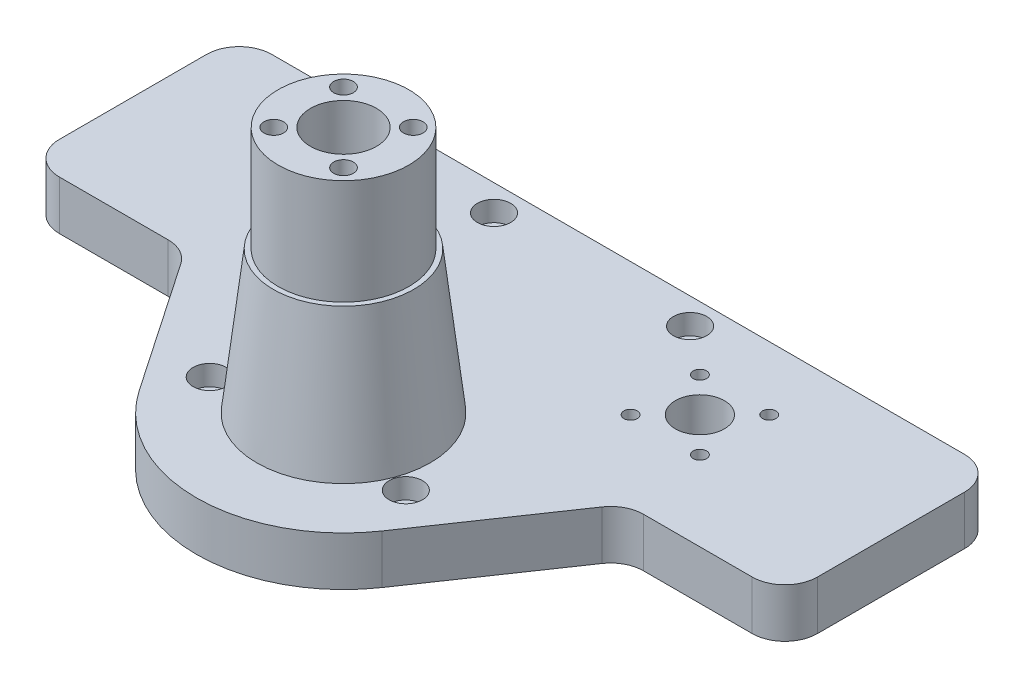
SolidWorks part; units mm, degrees
material "PLA Infill"
ref_plane "Front Plane" through (0, 0, 0) normal (0, 0, 1) x (1, 0, 0)
ref_plane "Top Plane" through (0, 0, 0) normal (0, 1, 0) x (1, 0, 0)
ref_plane "Right Plane" through (0, 0, 0) normal (1, 0, 0) x (0, 0, -1)
sketch "Sketch1" plane through (0, 0, 0) normal (0, 1, 0) x (1, 0, 0)
  line L0 (0, 0) -> (55, 54.0672) construction
  line L1 (55, 54.0672) -> (-55, 54.0672) construction
  line L2 (-55, 54.0672) -> (0, 0) construction
  line L3 (-79.7903, 37.1722) -> (-37.1854, -25.3425) construction
  line L4 (-55, 84.0672) -> (55, 84.0672)
  line L5 (37.1854, -25.3425) -> (79.7903, 37.1722) construction
  line L6 (-55, 84.0672) -> (-106, 84.0672)
  line L7 (-116, 74.0672) -> (-116, 29.0672)
  line L8 (-106, 19.0672) -> (-72.7378, 19.0672)
  line L9 (-64.4743, 14.6989) -> (-37.1854, -25.3425)
  line L10 (0, -1000) -> (0, 49000) construction
  line L11 (64.4743, 14.6989) -> (37.1854, -25.3425)
  line L12 (106, 19.0672) -> (72.7378, 19.0672)
  line L13 (116, 74.0672) -> (116, 29.0672)
  line L14 (55, 84.0672) -> (106, 84.0672)
  circle A0 centre (-55, 54.0672) radius 30 construction
  circle A1 centre (55, 54.0672) radius 30 construction
  circle A2 centre (0, 0) radius 45 construction
  arc A3 (-79.7903, 37.1722) -> (-55, 84.0672) centre (-55, 54.0672) cw construction
  arc A4 (55, 84.0672) -> (79.7903, 37.1722) centre (55, 54.0672) cw construction
  arc A5 (-37.1854, -25.3425) -> (37.1854, -25.3425) centre (0, 0) ccw
  arc A6 (-72.7378, 19.0672) -> (-64.4743, 14.6989) centre (-72.7378, 9.0672) cw
  arc A7 (-116, 29.0672) -> (-106, 19.0672) centre (-106, 29.0672) ccw
  arc A8 (-106, 84.0672) -> (-116, 74.0672) centre (-106, 74.0672) ccw
  arc A9 (72.7378, 19.0672) -> (64.4743, 14.6989) centre (72.7378, 9.0672) ccw
  arc A10 (116, 29.0672) -> (106, 19.0672) centre (106, 29.0672) cw
  arc A11 (106, 84.0672) -> (116, 74.0672) centre (106, 74.0672) cw
  point P23 (-67.4514, 19.0672)
  dimension "D3" = 60
  dimension "D4" = 90
  dimension "D5" = 10
  dimension "D6" = 61
  dimension "D1" = 110
  dimension "D2" = 77.125
  dimension "D7" = 35
extrude "Main Body" add sketch "Sketch1" along normal blind 15 contours A5 L11 A9 L12 A10 L13 A11 L14 L4 L6 A8 L7 A7 L8 A6 L9
sketch "Sketch3" plane through (0, 15, 0) normal (0, 1, 0) x (1, 0, 0)
  circle A0 centre (0, 0) radius 45 construction
  circle A1 centre (0, 0) radius 45 construction
  circle A2 centre (0, 0) radius 21.5
  dimension "D1" = 43
extrude "Front Extrusion" add sketch "Sketch3" along normal blind 75.7
ref_plane "First Bearing Section" through (0, 58.5, 0) normal (0, 1, 0) x (1, 0, 0)
sketch "Front Loft" plane through (0, 58.5, 0) normal (0, 1, 0) x (1, 0, 0)
  circle A0 centre (0, 0) radius 21.5
  dimension "D1" = 43
sketch "Back Loft" plane through (0, 15, 0) normal (0, 1, 0) x (1, 0, 0)
  circle A0 centre (0, 0) radius 26.5
  dimension "D1" = 53
loft "Lofted Taper" add profiles "Front Loft", "Back Loft" connector at (0, 58.5, 21.5) connector at (0, 15, 26.5)
sketch "Sketch4" plane through (0, 0, 0) normal (0, -1, 0) x (1, 0, 0)
  line L0 (0, -1000) -> (0, 49000) construction
  line L1 (-45, 0) -> (45, 0) construction
  line L2 (-85, -54.0672) -> (-25, -54.0672) construction
  line L3 (55, -54.0672) -> (-55, -54.0672) construction
  line L4 (-55, -24.0672) -> (-55, -84.0672) construction
  line L5 (-10.6773, 10.6773) -> (0, 0) construction
  line L6 (-10.6773, -10.6773) -> (0, 0) construction
  line L7 (-65.6066, -43.4606) -> (-55, -54.0672) construction
  line L8 (-106, -84.0672) -> (106, -84.0672) construction
  line L9 (106, -84.0672) -> (-106, -84.0672) construction
  line L10 (-30, -76.0672) -> (0, -76.0672) construction
  line L11 (-30, -76.0672) -> (-30, 10.9328) construction
  line L12 (-30, 10.9328) -> (0, 10.9328) construction
  line L13 (0, -76.0672) -> (0, 10.9328) construction
  circle A0 centre (55, -54.0672) radius 30 construction
  circle A1 centre (0, 0) radius 45 construction
  circle A2 centre (-55, -54.0672) radius 30 construction
  circle A3 centre (55, -54.0672) radius 30 construction
  circle A4 centre (0, 0) radius 45 construction
  circle A5 centre (-55, -54.0672) radius 30 construction
  circle A6 centre (0, 0) radius 10.1
  circle A7 centre (-55, -54.0672) radius 7.5
  circle A10 centre (-10.6773, 10.6773) radius 3
  circle A13 centre (-10.6773, -10.6773) radius 3
  circle A14 centre (-65.6066, -43.4606) radius 2.05
  circle A15 centre (-65.6066, -64.6738) radius 2.05
  circle A16 centre (-44.3934, -64.6738) radius 2.05
  circle A17 centre (-44.3934, -43.4606) radius 2.05
  circle A18 centre (55, -54.0672) radius 7.5
  circle A19 centre (65.6066, -64.6738) radius 2.05
  circle A20 centre (44.3934, -64.6738) radius 2.05
  circle A21 centre (44.3934, -43.4606) radius 2.05
  circle A22 centre (65.6066, -43.4606) radius 2.05
  circle A23 centre (10.6773, -10.6773) radius 3
  circle A24 centre (10.6773, 10.6773) radius 3
  circle A25 centre (-30, -76.0672) radius 3
  circle A26 centre (-30, 10.9328) radius 3
  circle A27 centre (30, -76.0672) radius 3
  circle A28 centre (30, 10.9328) radius 3
  dimension "D1" = 20.2
  dimension "D2" = 15
  dimension "D4" = 6
  dimension "D5" = 45
  dimension "D7" = 4.1
  dimension "D9" = 6
  dimension "D3" = 15.1
  dimension "D6" = 15
  dimension "D8" = 45
  dimension "D10" = 30
  dimension "D11" = 8
  dimension "D12" = 87
extrude "Bolt Holes" cut sketch "Sketch4" against normal through all
sketch "Sketch5" plane through (0, 0, 0) normal (0, -1, 0) x (1, 0, 0)
  line L0 (-14.2836, 7.0711) -> (-9.7707, 2.5582)
  line L1 (-7.0711, 14.2836) -> (-2.5582, 9.7707)
  line L2 (-10.6773, 10.6773) -> (0, 0) construction
  line L3 (-1000, 0) -> (49000, 0) construction
  line L4 (0, -1000) -> (0, 49000) construction
  line L5 (-14.2836, -7.0711) -> (-9.7707, -2.5582)
  line L6 (-7.0711, -14.2836) -> (-2.5582, -9.7707)
  line L7 (7.0711, -14.2836) -> (2.5582, -9.7707)
  line L8 (14.2836, -7.0711) -> (9.7707, -2.5582)
  line L9 (14.2836, 7.0711) -> (9.7707, 2.5582)
  line L10 (7.0711, 14.2836) -> (2.5582, 9.7707)
  circle A0 centre (-10.6773, 10.6773) radius 2 construction
  circle A1 centre (-10.6773, 10.6773) radius 5.1 construction
  circle A2 centre (0, 0) radius 10.1 construction
  arc A3 (-14.2836, 7.0711) -> (-7.0711, 14.2836) centre (-10.6773, 10.6773) cw
  circle A4 centre (0, 0) radius 10.1 construction
  arc A5 (-9.7707, 2.5582) -> (-2.5582, 9.7707) centre (0, 0) cw
  arc A6 (-14.2836, -7.0711) -> (-7.0711, -14.2836) centre (-10.6773, -10.6773) ccw
  arc A7 (-9.7707, -2.5582) -> (-2.5582, -9.7707) centre (0, 0) ccw
  arc A8 (14.2836, -7.0711) -> (7.0711, -14.2836) centre (10.6773, -10.6773) cw
  arc A9 (9.7707, -2.5582) -> (2.5582, -9.7707) centre (0, 0) cw
  arc A10 (14.2836, 7.0711) -> (7.0711, 14.2836) centre (10.6773, 10.6773) ccw
  arc A11 (9.7707, 2.5582) -> (2.5582, 9.7707) centre (0, 0) ccw
  dimension "D1" = 4
  dimension "D2" = 10.2
extrude "Bolt Recesses Rear" cut sketch "Sketch5" against normal blind 10
sketch "Sketch6" plane through (0, 15, 0) normal (0, 1, 0) x (1, 0, 0)
  circle A1 centre (30, 76.0672) radius 5.1
  circle A2 centre (-30, -10.9328) radius 3 construction
  circle A3 centre (30, -10.9328) radius 3 construction
  circle A4 centre (30, 76.0672) radius 3 construction
  circle A5 centre (-30, 76.0672) radius 3 construction
  circle A6 centre (-30, -10.9328) radius 3 construction
  circle A7 centre (30, -10.9328) radius 3 construction
  circle A8 centre (30, 76.0672) radius 3 construction
  circle A9 centre (-30, 76.0672) radius 3 construction
  circle A10 centre (-30, 76.0672) radius 5.1
  circle A11 centre (-30, -10.9328) radius 5.1
  circle A12 centre (30, -10.9328) radius 5.1
  dimension "D1" = 10.2
extrude "Bolt Recesses Front" cut sketch "Sketch6" against normal blind 6.2
sketch "Sketch7" plane through (0, 90.7, 0) normal (0, 1, 0) x (1, 0, 0)
  circle A0 centre (0, 0) radius 21.5 construction
  circle A1 centre (0, 0) radius 21.5
  circle A2 centre (0, 0) radius 20
  dimension "D1" = 40
extrude "Cut-Extrude1" cut sketch "Sketch7" against normal up to surface (32.2 mm away) up to plane "First Bearing Section"
sketch "Sketch8" plane through (0, 0, 0) normal (0, -1, 0) x (1, 0, 0)
  line L0 (0, -1000) -> (0, 49000) construction
  circle A0 centre (-65.6066, -64.6738) radius 2.05 construction
  circle A1 centre (-44.3934, -64.6738) radius 2.05 construction
  circle A2 centre (-44.3934, -43.4606) radius 2.05 construction
  circle A3 centre (-65.6066, -43.4606) radius 2.05 construction
  circle A4 centre (-65.6066, -64.6738) radius 2.05 construction
  circle A5 centre (-44.3934, -64.6738) radius 2.05 construction
  circle A6 centre (-44.3934, -43.4606) radius 2.05 construction
  circle A7 centre (-65.6066, -43.4606) radius 2.05 construction
  circle A8 centre (-65.6066, -43.4606) radius 3.55
  circle A9 centre (-44.3934, -43.4606) radius 3.55
  circle A10 centre (-44.3934, -64.6738) radius 3.55
  circle A11 centre (-65.6066, -64.6738) radius 3.55
  circle A12 centre (44.3934, -64.6738) radius 3.55
  circle A13 centre (44.3934, -43.4606) radius 3.55
  circle A14 centre (65.6066, -64.6738) radius 3.55
  circle A15 centre (65.6066, -43.4606) radius 3.55
  dimension "D1" = 7.1
extrude "Motor bolt head recesses" cut sketch "Sketch8" against normal blind 4.1
sketch "Sketch9" plane through (0, 0, 0) normal (0, -1, 0) x (1, 0, 0)
  line L0 (0, -1000) -> (0, 49000) construction
  line L1 (-116, -74.0672) -> (-116, -29.0672) construction
  line L2 (106, -84.0672) -> (-106, -84.0672) construction
  line L4 (-111, -75.0672) -> (-41, -75.0672) construction
  line L5 (-111, -75.0672) -> (-111, -28.0672) construction
  line L6 (-111, -28.0672) -> (-41, -28.0672) construction
  line L7 (-41, -75.0672) -> (-41, -28.0672) construction
  circle A0 centre (-111, -75.0672) radius 2
  circle A1 centre (-111, -28.0672) radius 2
  circle A2 centre (-41, -28.0672) radius 2
  circle A3 centre (-41, -75.0672) radius 2
  circle A4 centre (41, -75.0672) radius 2
  circle A5 centre (111, -75.0672) radius 2
  circle A6 centre (41, -28.0672) radius 2
  circle A7 centre (111, -28.0672) radius 2
  dimension "D3" = 4
  dimension "D1" = 5
  dimension "D2" = 9
  dimension "D4" = 70
  dimension "D5" = 47
extrude "Heat-set insert holes" cut sketch "Sketch9" against normal blind 6
sketch "Sketch10" plane through (0, 0, 0) normal (0, -1, 0) x (1, 0, 0)
  line L0 (0, -1000) -> (0, 49000) construction
  line L1 (-116, -74.0672) -> (-116, -29.0672) construction
  line L2 (106, -84.0672) -> (-106, -84.0672) construction
  line L4 (-101.5, -76.5672) -> (-51.5, -76.5672) construction
  line L5 (-101.5, -76.5672) -> (-101.5, -26.5672) construction
  line L6 (-101.5, -26.5672) -> (-51.5, -26.5672) construction
  line L7 (-51.5, -76.5672) -> (-51.5, -26.5672) construction
  circle A0 centre (-101.5, -76.5672) radius 1.6
  circle A1 centre (-101.5, -26.5672) radius 1.6
  circle A2 centre (-51.5, -26.5672) radius 1.6
  circle A3 centre (-51.5, -76.5672) radius 1.6
  circle A4 centre (101.5, -76.5672) radius 1.6
  circle A5 centre (51.5, -76.5672) radius 1.6
  circle A6 centre (51.5, -26.5672) radius 1.6
  circle A7 centre (101.5, -26.5672) radius 1.6
  dimension "D1" = 3.2
  dimension "D2" = 14.5
  dimension "D3" = 7.5
  dimension "D4" = 50
  dimension "D5" = 50
extrude "PCB Heat-set insert holes" cut sketch "Sketch10" against normal blind 4
sketch "Sketch11" plane through (0, 0, -84.0672) normal (0, 0, -1) x (-1, 0, 0)
  line L0 (0, -1000) -> (0, 49000) construction
  line L1 (-106, 0) -> (106, 0) construction
  circle A0 centre (-20, 7.5) radius 2
  circle A2 centre (20, 7.5) radius 2
  dimension "D1" = 4
  dimension "D2" = 7.5
  dimension "D3" = 20
extrude "Cut-Extrude2" cut sketch "Sketch11" against normal blind 6
